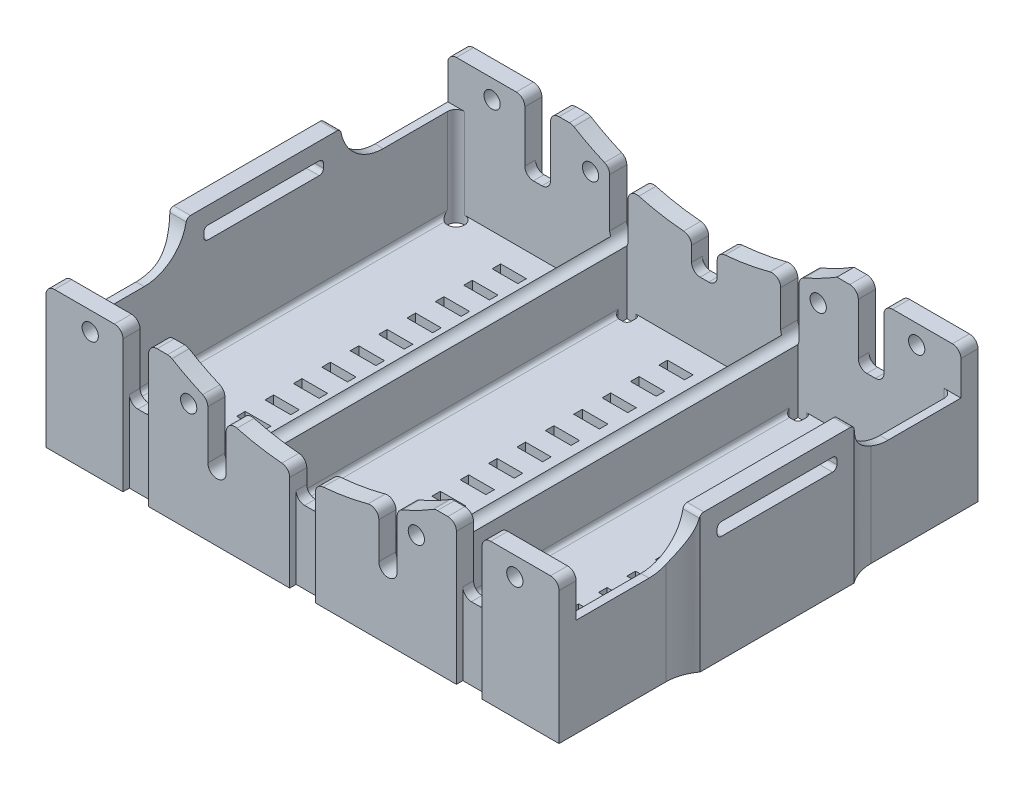
SolidWorks part; units mm, degrees
ref_plane "Front Plane" through (0, 0, 0) normal (0, 0, 1) x (1, 0, 0)
ref_plane "Top Plane" through (0, 0, 0) normal (0, 1, 0) x (1, 0, 0)
ref_plane "Right Plane" through (0, 0, 0) normal (1, 0, 0) x (0, 0, -1)
sketch "Sketch1" plane through (0, 0, 0) normal (0, 1, 0) x (1, 0, 0)
  line L1 (-60, -49) -> (60, -49)
  line L2 (-60, -49) -> (-60, 49)
  line L3 (-60, 49) -> (60, 49)
  line L4 (60, -49) -> (60, 49)
  line L5 (-60, -49) -> (60, 49) construction
  line L6 (-60, 49) -> (60, -49) construction
  point P0 (0, 0)
  dimension "D1" = 120
  dimension "D2" = 98
extrude "Boss-Extrude1" add sketch "Sketch1" along normal blind 2
sketch "Sketch3" plane through (0, 2, 0) normal (0, 1, 0) x (1, 0, 0)
  line L0 (20, 49) -> (20, 68.7594) construction
  line L1 (20, 68.7594) -> (-20, 68.7594) construction
  line L2 (60, 49) -> (-60, 49) construction
  line L3 (-21.8986, 49) -> (-18.1014, 49) construction
  line L4 (-21.8986, 49) -> (-21.8986, -49) construction
  line L5 (-60, -49) -> (60, -49) construction
  line L6 (-20, 68.7594) -> (-20, 49) construction
  line L7 (-18.1014, 49) -> (-18.1014, -49) construction
  line L8 (-18.1014, -49) -> (18.1014, 49) construction
  line L9 (18.1014, 49) -> (18.1014, -49) construction
  line L10 (18.1014, 49) -> (21.8986, 49) construction
  line L11 (21.8986, 49) -> (21.8986, -49) construction
  line L12 (0, 0) -> (0, 49) construction
  line L13 (-18.1014, 49) -> (-16.3514, 49) construction
  line L14 (-18.1014, 49) -> (-18.1014, -49) construction
  line L15 (-18.1014, -49) -> (-16.3514, -49) construction
  line L16 (-16.3514, 49) -> (-16.3514, -49) construction
  line L17 (-23.6486, 49) -> (-21.8986, 49) construction
  line L18 (-23.6486, 49) -> (-23.6486, -49) construction
  line L19 (-23.6486, -49) -> (-21.8986, -49) construction
  line L20 (-21.8986, 49) -> (-21.8986, -49) construction
  line L21 (21.8986, 49) -> (21.8986, -49) construction
  line L22 (23.6486, -49) -> (21.8986, -49) construction
  line L23 (23.6486, 49) -> (23.6486, -49) construction
  line L24 (23.6486, 49) -> (21.8986, 49) construction
  line L25 (16.3514, 49) -> (16.3514, -49) construction
  line L26 (18.1014, -49) -> (16.3514, -49) construction
  line L27 (18.1014, 49) -> (18.1014, -49) construction
  line L28 (18.1014, 49) -> (16.3514, 49) construction
  line L30 (-21.8986, 49) -> (-18.1014, 49)
  line L31 (-21.8986, 49) -> (-21.8986, -49)
  line L32 (-21.8986, -49) -> (-18.1014, -49)
  line L33 (-18.1014, 49) -> (-18.1014, -49)
  line L34 (18.1014, -49) -> (21.8986, -49)
  line L35 (18.1014, -49) -> (18.1014, 49)
  line L36 (18.1014, 49) -> (21.8986, 49)
  line L37 (21.8986, -49) -> (21.8986, 49)
  dimension "D1" = 3.7973
  dimension "D2" = 40
  dimension "D3" = 1.75
extrude "Boss-Extrude3" add sketch "Sketch3" along normal blind 21
sketch "Sketch4" plane through (0, 2, 0) normal (0, 1, 0) x (1, 0, 0)
  line L1 (-60, 49) -> (-21.8986, 49)
  line L2 (-60, 49) -> (-60, 45)
  line L3 (-60, 45) -> (-21.8986, 45)
  line L4 (-21.8986, 49) -> (-21.8986, 45)
  line L6 (-18.1014, 49) -> (18.1014, 49)
  line L7 (-18.1014, 49) -> (-18.1014, 45)
  line L8 (-18.1014, 45) -> (18.1014, 45)
  line L9 (18.1014, 49) -> (18.1014, 45)
  line L10 (60, -49) -> (60, 49) construction
  line L11 (21.8986, 49) -> (60, 49)
  line L12 (21.8986, 49) -> (21.8986, 45)
  line L13 (21.8986, 45) -> (60, 45)
  line L14 (60, 49) -> (60, 45)
  line L15 (-18.1014, -49) -> (-18.1014, 49) construction
  line L16 (-21.8986, 49) -> (-21.8986, -49) construction
  line L17 (21.8986, -49) -> (21.8986, 49) construction
  line L18 (18.1014, 49) -> (18.1014, -49) construction
  line L19 (18.1014, 49) -> (-18.1014, 49) construction
  line L20 (18.1014, 49) -> (18.1014, -49) construction
  line L21 (-60, -49) -> (-21.8986, -49)
  line L22 (-60, -49) -> (-60, -45)
  line L23 (-60, -45) -> (-21.8986, -45)
  line L24 (-21.8986, -49) -> (-21.8986, -45)
  line L25 (-18.1014, -49) -> (18.1014, -49)
  line L26 (-18.1014, -49) -> (-18.1014, -45)
  line L27 (-18.1014, -45) -> (18.1014, -45)
  line L28 (18.1014, -49) -> (18.1014, -45)
  line L30 (21.8986, -49) -> (60, -49)
  line L31 (21.8986, -49) -> (21.8986, -45)
  line L32 (21.8986, -45) -> (60, -45)
  line L33 (60, -49) -> (60, -45)
  dimension "D1" = 4
extrude "Boss-Extrude4" add sketch "Sketch4" along normal up to surface (21 mm away) up to face at (-20, 23, 0)
sketch "Sketch5" plane through (0, 0, 49) normal (0, 0, 1) x (1, 0, 0)
  line L0 (-22.1487, 15.8) -> (-22.1487, 23)
  line L1 (-22.1487, 23) -> (-17.8514, 23)
  line L2 (-17.8514, 23) -> (-17.8514, 15.8)
  line L3 (-60, 23) -> (60, 23) construction
  line L4 (17.8514, 15.8) -> (17.8514, 23)
  line L6 (17.8514, 23) -> (22.1487, 23)
  line L7 (22.1487, 23) -> (22.1487, 15.8)
  line L8 (-60, 23) -> (60, 23) construction
  circle A2 centre (20, 15.8) radius 1.8986 construction
  circle A3 centre (-20, 15.8) radius 1.8986 construction
  arc A6 (-22.1487, 15.8) -> (-17.8514, 15.8) centre (-20, 15.8) ccw
  arc A7 (17.8514, 15.8) -> (22.1487, 15.8) centre (20, 15.8) ccw
  circle A9 centre (-20, 15.8) radius 2.1486 construction
  circle A10 centre (20, 15.8) radius 2.1486 construction
  point P14 (-17.9452, 16.4282)
  point P18 (22.0548, 16.4282)
  dimension "D1" = 0.25
extrude "Cut-Extrude1" cut sketch "Sketch5" against normal through all both and the other way through all
sketch "Sketch6" plane through (0, 2, 0) normal (0, 1, 0) x (1, 0, 0)
  line L0 (-60, 45) -> (-21.8986, 45) construction
  line L1 (-60, -49) -> (-58.1, -49)
  line L2 (-60, -49) -> (-60, 45)
  line L3 (-60, 45) -> (-58.1, 45)
  line L4 (-58.1, -49) -> (-58.1, 45)
  line L5 (21.8986, 45) -> (60, 45) construction
  line L6 (60, -49) -> (58.1, -49)
  line L7 (60, -49) -> (60, 45)
  line L8 (60, 45) -> (58.1, 45)
  line L9 (58.1, -49) -> (58.1, 45)
  dimension "D1" = 1.9
extrude "Boss-Extrude5" add sketch "Sketch6" along normal up to surface (21 mm away) up to face at (-41.0743, 23, -47)
sketch "Sketch9" plane through (0, 0, -45) normal (0, 0, 1) x (1, 0, 0)
  line L1 (0, 24.2) -> (0, 44.7462) construction
  line L2 (-30.9994, 33) -> (-60, 33)
  line L4 (-60, 23) -> (-60, 0) construction
  line L5 (-60, 33) -> (-60, 23)
  line L6 (-60, 23) -> (60, 23)
  line L7 (-17.8514, 23) -> (17.8514, 23) construction
  line L8 (0, 23) -> (0, 24.2) construction
  line L9 (60, 33) -> (60, 23)
  line L10 (30.9994, 33) -> (60, 33)
  line L11 (-60, 23) -> (-60, 0) construction
  arc A4 (30.9994, 33) -> (-30.9994, 33) centre (0, 83.2) cw
  circle A6 centre (-49.6579, 28.5871) radius 1.8987
  circle A8 centre (49.6579, 28.5871) radius 1.8987
  circle A10 centre (26.625, 25.5492) radius 1.8987
  circle A12 centre (-26.625, 25.5492) radius 1.8987
  dimension "D1" = 10
extrude "Boss-Extrude6" add sketch "Sketch9" against normal up to surface (4 mm away) up to face at (0, 16.4086, -49)
sketch "Sketch10" plane through (0, 0, 49) normal (0, 0, 1) x (1, 0, 0)
  line L0 (60, 23) -> (60, 33) construction
  line L1 (60, 33) -> (30.9994, 33) construction
  line L2 (-30.9994, 33) -> (-60, 33) construction
  line L3 (-60, 33) -> (-60, 23) construction
  line L4 (60, 23) -> (60, 33)
  line L5 (60, 33) -> (30.9994, 33)
  line L6 (-30.9994, 33) -> (-60, 33)
  line L7 (-60, 33) -> (-60, 23)
  line L8 (-60, 23) -> (60, 23)
  circle A0 centre (49.6579, 28.5871) radius 1.8987 construction
  circle A1 centre (26.625, 25.5492) radius 1.8987 construction
  circle A2 centre (-26.625, 25.5492) radius 1.8987 construction
  circle A3 centre (-49.6579, 28.5871) radius 1.8987 construction
  arc A4 (-30.9994, 33) -> (30.9994, 33) centre (0, 83.2) ccw construction
  circle A5 centre (49.6579, 28.5871) radius 1.8987
  circle A6 centre (26.625, 25.5492) radius 1.8987
  circle A7 centre (-26.625, 25.5492) radius 1.8987
  circle A8 centre (-49.6579, 28.5871) radius 1.8987
  arc A9 (-30.9994, 33) -> (30.9994, 33) centre (0, 83.2) ccw
extrude "Boss-Extrude7" add sketch "Sketch10" against normal up to surface (4 mm away) up to face at (-34.0594, 13.4298, 45)
sketch "Sketch11" plane through (0, 0, 49) normal (0, 0, 1) x (1, 0, 0)
  line L0 (-17.8514, 23) -> (-17.8514, 15.8) construction
  line L1 (-22.1487, 23) -> (-17.8514, 23)
  line L2 (-22.1487, 23) -> (-22.1487, 43)
  line L3 (-22.1487, 43) -> (-17.8514, 43)
  line L4 (-17.8514, 23) -> (-17.8514, 43)
  line L6 (22.1487, 23) -> (17.8514, 23)
  line L7 (22.1487, 23) -> (22.1487, 43)
  line L8 (22.1487, 43) -> (17.8514, 43)
  line L9 (17.8514, 23) -> (17.8514, 43)
  dimension "D1" = 20
extrude "Cut-Extrude4" cut sketch "Sketch11" against normal through all both
fillet "Fillet2" radius 2 4 edges at (-58.1, 12.5, 45) (-58.1, 12.5, -45) (58.1, 12.5, 45) (58.1, 12.5, -45)
fillet "Fillet3" radius 2 15 edges at (60, 33, 47) (30.9994, 33, 47) (-30.9994, 33, -47) (-30.9994, 33, 47) (22.1487, 28.5151, 47) (17.8514, 26.9654, 47) (-17.8514, 26.9654, 47) (-22.1487, 28.5151, 47) (-60, 33, 47) (-60, 33, -47) (60, 33, -47) (22.1487, 28.5151, -47) (17.8514, 26.9654, -47) (-22.1487, 28.5151, -47) (-17.8514, 26.9654, -47)
sketch "Sketch12" plane through (0, 2, 0) normal (0, 1, 0) x (1, 0, 0)
  line L0 (0, -45) -> (0, 45) construction
  line L1 (18.1014, -45) -> (-18.1014, -45) construction
  line L2 (-18.1014, 45) -> (18.1014, 45) construction
  line L4 (-3, 39.36) -> (3, 39.36)
  line L5 (-3, 39.36) -> (-3, 37.36)
  line L6 (-3, 37.36) -> (3, 37.36)
  line L7 (3, 39.36) -> (3, 37.36)
  line L10 (-38.9993, 45) -> (-38.9993, -45) construction
  line L11 (-56.1, 45) -> (-21.8986, 45) construction
  line L12 (-21.8986, -45) -> (-56.1, -45) construction
  line L13 (3, 38.36) -> (8.9563, 38.36) construction
  line L14 (-38.9993, 0) -> (0, 0) construction
  line L15 (-19.4997, 0) -> (-19.4997, 39.7197) construction
  line L16 (-3, 32.72) -> (-3, 30.72)
  line L17 (-3, 32.72) -> (3, 32.72)
  line L18 (3, 32.72) -> (3, 30.72)
  line L19 (-3, 30.72) -> (3, 30.72)
  line L20 (-3, 26.08) -> (-3, 24.08)
  line L21 (-3, 26.08) -> (3, 26.08)
  line L22 (3, 26.08) -> (3, 24.08)
  line L23 (-3, 24.08) -> (3, 24.08)
  line L24 (-3, 19.44) -> (-3, 17.44)
  line L25 (-3, 19.44) -> (3, 19.44)
  line L26 (3, 19.44) -> (3, 17.44)
  line L27 (-3, 17.44) -> (3, 17.44)
  line L28 (-3, 12.8) -> (-3, 10.8)
  line L29 (-3, 12.8) -> (3, 12.8)
  line L30 (3, 12.8) -> (3, 10.8)
  line L31 (-3, 10.8) -> (3, 10.8)
  line L32 (-3, 6.16) -> (-3, 4.16)
  line L33 (-3, 6.16) -> (3, 6.16)
  line L34 (3, 6.16) -> (3, 4.16)
  line L35 (-3, 4.16) -> (3, 4.16)
  line L36 (-3, -0.48) -> (-3, -2.48)
  line L37 (-3, -0.48) -> (3, -0.48)
  line L38 (3, -0.48) -> (3, -2.48)
  line L39 (-3, -2.48) -> (3, -2.48)
  line L40 (-3, -7.12) -> (-3, -9.12)
  line L41 (-3, -7.12) -> (3, -7.12)
  line L42 (3, -7.12) -> (3, -9.12)
  line L43 (-3, -9.12) -> (3, -9.12)
  line L44 (-3, -13.76) -> (-3, -15.76)
  line L45 (-3, -13.76) -> (3, -13.76)
  line L46 (3, -13.76) -> (3, -15.76)
  line L47 (-3, -15.76) -> (3, -15.76)
  line L48 (-3, -20.4) -> (-3, -22.4)
  line L49 (-3, -20.4) -> (3, -20.4)
  line L50 (3, -20.4) -> (3, -22.4)
  line L51 (-3, -22.4) -> (3, -22.4)
  line L52 (-3, -27.04) -> (-3, -29.04)
  line L53 (-3, -27.04) -> (3, -27.04)
  line L54 (3, -27.04) -> (3, -29.04)
  line L55 (-3, -29.04) -> (3, -29.04)
  line L56 (-3, -33.68) -> (-3, -35.68)
  line L57 (-3, -33.68) -> (3, -33.68)
  line L58 (3, -33.68) -> (3, -35.68)
  line L59 (-3, -35.68) -> (3, -35.68)
  line L60 (-3, -40.32) -> (-3, -42.32)
  line L61 (-3, -40.32) -> (3, -40.32)
  line L62 (3, -40.32) -> (3, -42.32)
  line L63 (-3, -42.32) -> (3, -42.32)
  line L71 (-35.9993, -42.32) -> (-41.9993, -42.32)
  line L72 (-35.9993, -40.32) -> (-41.9993, -40.32)
  line L73 (-35.9993, -40.32) -> (-35.9993, -42.32)
  line L74 (-35.9993, -35.68) -> (-41.9993, -35.68)
  line L75 (-35.9993, -33.68) -> (-41.9993, -33.68)
  line L76 (-35.9993, -33.68) -> (-35.9993, -35.68)
  line L77 (-41.9993, 39.36) -> (-41.9993, 37.36)
  line L78 (-35.9993, 37.36) -> (-41.9993, 37.36)
  line L79 (-35.9993, 39.36) -> (-41.9993, 39.36)
  line L81 (-41.9993, -40.32) -> (-41.9993, -42.32)
  line L82 (-41.9993, -33.68) -> (-41.9993, -35.68)
  line L83 (-35.9993, -29.04) -> (-41.9993, -29.04)
  line L84 (-41.9993, -27.04) -> (-41.9993, -29.04)
  line L85 (-35.9993, -27.04) -> (-41.9993, -27.04)
  line L86 (-35.9993, -27.04) -> (-35.9993, -29.04)
  line L87 (-35.9993, -22.4) -> (-41.9993, -22.4)
  line L88 (-41.9993, -20.4) -> (-41.9993, -22.4)
  line L89 (-35.9993, -20.4) -> (-41.9993, -20.4)
  line L90 (-35.9993, -20.4) -> (-35.9993, -22.4)
  line L91 (-35.9993, -15.76) -> (-41.9993, -15.76)
  line L92 (-41.9993, -13.76) -> (-41.9993, -15.76)
  line L93 (-35.9993, -13.76) -> (-41.9993, -13.76)
  line L94 (-35.9993, -13.76) -> (-35.9993, -15.76)
  line L95 (-35.9993, -9.12) -> (-41.9993, -9.12)
  line L96 (-41.9993, -7.12) -> (-41.9993, -9.12)
  line L97 (-35.9993, -7.12) -> (-41.9993, -7.12)
  line L98 (-35.9993, -7.12) -> (-35.9993, -9.12)
  line L99 (-35.9993, -2.48) -> (-41.9993, -2.48)
  line L100 (-41.9993, -0.48) -> (-41.9993, -2.48)
  line L101 (-35.9993, -0.48) -> (-41.9993, -0.48)
  line L102 (-35.9993, -0.48) -> (-35.9993, -2.48)
  line L103 (-35.9993, 4.16) -> (-41.9993, 4.16)
  line L104 (-41.9993, 6.16) -> (-41.9993, 4.16)
  line L105 (-35.9993, 6.16) -> (-41.9993, 6.16)
  line L106 (-35.9993, 6.16) -> (-35.9993, 4.16)
  line L107 (-35.9993, 10.8) -> (-41.9993, 10.8)
  line L108 (-41.9993, 12.8) -> (-41.9993, 10.8)
  line L109 (-35.9993, 12.8) -> (-41.9993, 12.8)
  line L110 (-35.9993, 12.8) -> (-35.9993, 10.8)
  line L111 (-35.9993, 17.44) -> (-41.9993, 17.44)
  line L112 (-41.9993, 19.44) -> (-41.9993, 17.44)
  line L113 (-35.9993, 19.44) -> (-41.9993, 19.44)
  line L114 (-35.9993, 19.44) -> (-35.9993, 17.44)
  line L115 (-35.9993, 24.08) -> (-41.9993, 24.08)
  line L116 (-41.9993, 26.08) -> (-41.9993, 24.08)
  line L117 (-35.9993, 26.08) -> (-41.9993, 26.08)
  line L118 (-35.9993, 26.08) -> (-35.9993, 24.08)
  line L119 (-35.9993, 30.72) -> (-41.9993, 30.72)
  line L120 (-41.9993, 32.72) -> (-41.9993, 30.72)
  line L121 (-35.9993, 32.72) -> (-41.9993, 32.72)
  line L122 (-35.9993, 32.72) -> (-35.9993, 30.72)
  line L123 (-35.9993, 39.36) -> (-35.9993, 37.36)
  line L124 (35.9993, 39.36) -> (35.9993, 37.36)
  line L125 (35.9993, 32.72) -> (35.9993, 30.72)
  line L126 (35.9993, 32.72) -> (41.9993, 32.72)
  line L127 (41.9993, 32.72) -> (41.9993, 30.72)
  line L128 (35.9993, 30.72) -> (41.9993, 30.72)
  line L129 (35.9993, 26.08) -> (35.9993, 24.08)
  line L130 (35.9993, 26.08) -> (41.9993, 26.08)
  line L131 (41.9993, 26.08) -> (41.9993, 24.08)
  line L132 (35.9993, 24.08) -> (41.9993, 24.08)
  line L133 (35.9993, 19.44) -> (35.9993, 17.44)
  line L134 (35.9993, 19.44) -> (41.9993, 19.44)
  line L135 (41.9993, 19.44) -> (41.9993, 17.44)
  line L136 (35.9993, 17.44) -> (41.9993, 17.44)
  line L137 (35.9993, 12.8) -> (35.9993, 10.8)
  line L138 (35.9993, 12.8) -> (41.9993, 12.8)
  line L139 (41.9993, 12.8) -> (41.9993, 10.8)
  line L140 (35.9993, 10.8) -> (41.9993, 10.8)
  line L141 (35.9993, 6.16) -> (35.9993, 4.16)
  line L142 (35.9993, 6.16) -> (41.9993, 6.16)
  line L143 (41.9993, 6.16) -> (41.9993, 4.16)
  line L144 (35.9993, 4.16) -> (41.9993, 4.16)
  line L145 (35.9993, -0.48) -> (35.9993, -2.48)
  line L146 (35.9993, -0.48) -> (41.9993, -0.48)
  line L147 (41.9993, -0.48) -> (41.9993, -2.48)
  line L148 (35.9993, -2.48) -> (41.9993, -2.48)
  line L149 (35.9993, -7.12) -> (35.9993, -9.12)
  line L150 (35.9993, -7.12) -> (41.9993, -7.12)
  line L151 (41.9993, -7.12) -> (41.9993, -9.12)
  line L152 (35.9993, -9.12) -> (41.9993, -9.12)
  line L153 (35.9993, -13.76) -> (35.9993, -15.76)
  line L154 (35.9993, -13.76) -> (41.9993, -13.76)
  line L155 (41.9993, -13.76) -> (41.9993, -15.76)
  line L156 (35.9993, -15.76) -> (41.9993, -15.76)
  line L157 (35.9993, -20.4) -> (35.9993, -22.4)
  line L158 (35.9993, -20.4) -> (41.9993, -20.4)
  line L159 (41.9993, -20.4) -> (41.9993, -22.4)
  line L160 (35.9993, -22.4) -> (41.9993, -22.4)
  line L161 (35.9993, -27.04) -> (35.9993, -29.04)
  line L162 (35.9993, -27.04) -> (41.9993, -27.04)
  line L163 (41.9993, -27.04) -> (41.9993, -29.04)
  line L164 (35.9993, -29.04) -> (41.9993, -29.04)
  line L165 (41.9993, -33.68) -> (41.9993, -35.68)
  line L166 (41.9993, -40.32) -> (41.9993, -42.32)
  line L168 (35.9993, 39.36) -> (41.9993, 39.36)
  line L169 (35.9993, 37.36) -> (41.9993, 37.36)
  line L170 (41.9993, 39.36) -> (41.9993, 37.36)
  line L171 (35.9993, -33.68) -> (35.9993, -35.68)
  line L172 (35.9993, -33.68) -> (41.9993, -33.68)
  line L173 (35.9993, -35.68) -> (41.9993, -35.68)
  line L174 (35.9993, -40.32) -> (35.9993, -42.32)
  line L175 (35.9993, -40.32) -> (41.9993, -40.32)
  line L176 (35.9993, -42.32) -> (41.9993, -42.32)
  point P22 (0, 39.36)
  dimension "D1" = 6
  dimension "D2" = 6.64
  dimension "D3" = 2
  dimension "D4" = 13
extrude "Cut-Extrude5" cut sketch "Sketch12" against normal through all both
sketch "Sketch13" plane through (0, 0, 49) normal (0, 0, 1) x (1, 0, 0)
  line L0 (41.9993, 2) -> (35.9993, 2) construction
  line L1 (3, 2) -> (-3, 2) construction
  line L2 (-35.9993, 2) -> (-41.9993, 2) construction
  line L3 (41.9993, 2) -> (35.9993, 2) construction
  line L4 (3, 2) -> (-3, 2) construction
  line L5 (-35.9993, 2) -> (-41.9993, 2) construction
  line L6 (-41.9993, 17) -> (-35.9993, 17)
  line L7 (-3, 17) -> (-35.9993, 17) construction
  line L8 (-3, 17) -> (3, 17)
  line L9 (-35.9993, 17) -> (-3, 2) construction
  line L10 (35.9993, 17) -> (41.9993, 17)
  line L11 (-3, 17) -> (-3, 2) construction
  line L12 (3, 17) -> (35.9993, 17) construction
  line L13 (-35.9993, 17) -> (-35.9993, 2) construction
  line L14 (-35.9993, 2) -> (-41.9993, 17) construction
  line L15 (-41.9993, 17) -> (-41.9993, 2) construction
  line L16 (-3, 2) -> (3, 17) construction
  line L17 (3, 17) -> (3, 2) construction
  line L18 (-41.9993, 17) -> (-41.9993, 47)
  line L19 (-41.9993, 47) -> (-35.9993, 47)
  line L20 (-35.9993, 47) -> (-35.9993, 17)
  line L21 (-3, 17) -> (-3, 47)
  line L22 (-3, 47) -> (3, 47)
  line L23 (3, 47) -> (3, 17)
  line L24 (35.9993, 17) -> (35.9993, 47)
  line L25 (35.9993, 47) -> (41.9993, 47)
  line L26 (41.9993, 47) -> (41.9993, 17)
  dimension "D1" = 15
  dimension "D2" = 30
extrude "Cut-Extrude6" cut sketch "Sketch13" against normal through all both
sketch "Sketch19" plane through (0, 17, 0) normal (0, 1, 0) x (1, 0, 0)
  line L5 (-35.9993, 49) -> (-35.9993, 45) construction
  line L6 (-41.9993, 49) -> (-35.9993, 49)
  line L7 (-41.9993, 49) -> (-41.9993, 47.5)
  line L8 (-41.9993, 47.5) -> (-35.9993, 47.5)
  line L9 (-35.9993, 49) -> (-35.9993, 47.5)
  line L10 (3, 45) -> (3, 49) construction
  line L11 (-3, 49) -> (3, 49)
  line L12 (-3, 49) -> (-3, 47.5)
  line L13 (-3, 47.5) -> (3, 47.5)
  line L14 (3, 49) -> (3, 47.5)
  line L15 (41.9993, 45) -> (41.9993, 49) construction
  line L16 (35.9993, 49) -> (41.9993, 49)
  line L17 (35.9993, 49) -> (35.9993, 47.5)
  line L18 (35.9993, 47.5) -> (41.9993, 47.5)
  line L19 (41.9993, 49) -> (41.9993, 47.5)
  line L20 (0, 0) -> (11.3492, 0) construction
  line L21 (41.9993, -49) -> (41.9993, -47.5)
  line L22 (35.9993, -47.5) -> (41.9993, -47.5)
  line L23 (35.9993, -49) -> (35.9993, -47.5)
  line L24 (35.9993, -49) -> (41.9993, -49)
  line L25 (3, -49) -> (3, -47.5)
  line L26 (-3, -47.5) -> (3, -47.5)
  line L27 (-3, -49) -> (-3, -47.5)
  line L28 (-3, -49) -> (3, -49)
  line L29 (-35.9993, -49) -> (-35.9993, -47.5)
  line L30 (-41.9993, -47.5) -> (-35.9993, -47.5)
  line L31 (-41.9993, -49) -> (-41.9993, -47.5)
  line L32 (-41.9993, -49) -> (-35.9993, -49)
  dimension "D1" = 1.5
extrude "Cut-Extrude9" cut sketch "Sketch19" against normal through all
fillet "Fillet4" radius 2 24 edges at (41.9993, 33, -47) (41.9993, 17, -46.25) (35.9993, 33, -47) (35.9993, 17, -46.25) (3, 24.2763, -47) (-3, 24.2763, -47) (-3, 17, -46.25) (3, 17, -46.25) (-35.9993, 33, -47) (-35.9993, 17, -46.25) (-41.9993, 33, -47) (-41.9993, 17, -46.25) (41.9993, 33, 47) (41.9993, 17, 46.25) (35.9993, 33, 47) (35.9993, 17, 46.25) (-3, 17, 46.25) (3, 17, 46.25) (3, 24.2763, 47) (-3, 24.2763, 47) (-35.9993, 33, 47) (-35.9993, 17, 46.25) (-41.9993, 17, 46.25) (-41.9993, 33, 47)
sketch "Sketch14" plane through (0, 2, 0) normal (0, 1, 0) x (1, 0, 0)
  line L0 (0, 45) -> (0, -45) construction
  line L1 (-18.1014, 45) -> (18.1014, 45) construction
  line L2 (18.1014, -45) -> (-18.1014, -45) construction
  line L3 (0, -45) -> (-58.1, 0) construction
  line L4 (-58.1, -43) -> (-58.1, 43) construction
  line L5 (-58.1, 0) -> (0, 0) construction
  line L6 (-18.1014, 45) -> (18.1014, 45) construction
  line L7 (24.8986, 45) -> (24.8986, 42)
  line L8 (-18.1014, 45) -> (-15.1014, 45)
  line L9 (-18.1014, 45) -> (-18.1014, 42)
  line L10 (-18.1014, 42) -> (-15.1014, 42)
  line L11 (-15.1014, 45) -> (-15.1014, 42)
  line L12 (-21.8986, 45) -> (-24.8986, 45)
  line L13 (-21.8986, 45) -> (-21.8986, 42)
  line L14 (-21.8986, 42) -> (-24.8986, 42)
  line L15 (-24.8986, 45) -> (-24.8986, 42)
  line L16 (21.8986, 42) -> (24.8986, 42)
  line L17 (21.8986, 45) -> (21.8986, 42)
  line L18 (21.8986, 45) -> (24.8986, 45)
  line L19 (15.1014, 45) -> (15.1014, 42)
  line L20 (18.1014, 42) -> (15.1014, 42)
  line L21 (18.1014, 45) -> (18.1014, 42)
  line L22 (18.1014, 45) -> (15.1014, 45)
  line L23 (-18.1014, -45) -> (18.1014, -45) construction
  line L24 (18.1014, -45) -> (15.1014, -45)
  line L25 (18.1014, -45) -> (18.1014, -42)
  line L26 (18.1014, -42) -> (15.1014, -42)
  line L27 (15.1014, -45) -> (15.1014, -42)
  line L28 (21.8986, -45) -> (24.8986, -45)
  line L29 (21.8986, -45) -> (21.8986, -42)
  line L30 (21.8986, -42) -> (24.8986, -42)
  line L31 (-24.8986, -45) -> (-24.8986, -42)
  line L32 (-21.8986, -42) -> (-24.8986, -42)
  line L33 (-21.8986, -45) -> (-21.8986, -42)
  line L34 (-21.8986, -45) -> (-24.8986, -45)
  line L35 (-15.1013, -45) -> (-15.1013, -42)
  line L36 (-18.1013, -42) -> (-15.1013, -42)
  line L37 (-18.1014, -45) -> (-18.1013, -42)
  line L38 (-18.1014, -45) -> (-15.1013, -45)
  line L39 (24.8986, -45) -> (24.8986, -42)
  circle A0 centre (-56.1, 43) radius 2
  arc A5 (-56.1, 45) -> (-58.1, 43) centre (-56.1, 43) ccw construction
  circle A6 centre (56.1, 43) radius 2
  circle A7 centre (56.1, -43) radius 2
  circle A8 centre (-56.1, -43) radius 2
  dimension "D1" = 3
extrude "Cut-Extrude7" cut sketch "Sketch14" against normal through all both
fillet "Fillet5" radius 1 24 edges at (-15.1013, 1, 45) (-15.1013, 1, 42) (-24.8986, 1, 45) (-24.8986, 1, 42) (15.1014, 1, 42) (15.1014, 1, 45) (24.8986, 1, 42) (24.8986, 1, 45) (24.8986, 1, -42) (24.8986, 1, -45) (15.1014, 1, -45) (15.1014, 1, -42) (-15.1014, 1, -45) (-15.1014, 1, -42) (-24.8986, 1, -42) (-24.8986, 1, -45) (-21.8986, 1, 42) (-18.1013, 1, 42) (18.1014, 1, 42) (21.8986, 1, 42) (18.1014, 1, -42) (21.8986, 1, -42) (-18.1014, 1, -42) (-21.8986, 1, -42)
sketch "Sketch16" plane through (0, 0, 0) normal (0, -1, 0) x (1, 0, 0)
  line L0 (-60, 0) -> (-76.8023, 0) construction
  line L1 (-60, -49) -> (-60, 49) construction
  line L2 (-76.8023, 14) -> (-76.8023, -14) construction
  line L3 (-62, -18) -> (-60, -18)
  line L4 (-62, -18) -> (-62, 18)
  line L5 (-62, 18) -> (-60, 18)
  line L6 (-60, -18) -> (-60, 18)
  line L7 (0, 0) -> (0, 45.5427) construction
  line L9 (62, 18) -> (60, 18)
  line L10 (60, -18) -> (60, 18)
  line L11 (62, -18) -> (60, -18)
  line L12 (62, -18) -> (62, 18)
  point P9 (-60, 0)
  point P11 (-76.8023, 0)
  point P15 (0, 45.5427)
  dimension "D1" = 2
  dimension "D2" = 4
  dimension "D3" = 28
extrude "Boss-Extrude8" add sketch "Sketch16" against normal up to surface (23 mm away)
sketch "Sketch17" plane through (0, 23, 0) normal (0, 1, 0) x (1, 0, 0)
  line L0 (-62, 18) -> (-58.1, 18)
  line L1 (-58.1, -43) -> (-58.1, 43) construction
  line L2 (-58.1, 18) -> (-58.1, -18)
  line L3 (-58.1, -43) -> (-58.1, 43) construction
  line L4 (-58.1, -18) -> (-62, -18)
  line L5 (-62, -18) -> (-62, 18)
  line L6 (-60, -18) -> (-62, -18) construction
  line L7 (0, 0) -> (0, 28.2857) construction
  line L8 (58.1, -18) -> (62, -18)
  line L9 (58.1, 18) -> (58.1, -18)
  line L10 (62, 18) -> (58.1, 18)
  line L11 (62, -18) -> (62, 18)
extrude "Boss-Extrude9" add sketch "Sketch17" along normal blind 9
sketch "Sketch18" plane through (-62, 0, 0) normal (-1, 0, 0) x (0, 0, 1)
  line L0 (-45, 23) -> (-18, 23) construction
  line L1 (-14, 28) -> (14, 28)
  line L2 (-14, 28) -> (-14, 25)
  line L3 (-14, 25) -> (14, 25)
  line L4 (14, 28) -> (14, 25)
  line L5 (-45, 23) -> (-18, 23) construction
  line L6 (0, 0) -> (0, 25) construction
  line L7 (-18, 32) -> (-18, 0) construction
  line L8 (-18, 32) -> (18, 32) construction
  dimension "D1" = 4
  dimension "D2" = 4
  dimension "D3" = 3
extrude "Cut-Extrude8" cut sketch "Sketch18" against normal through all
fillet "Fillet6" radius 10 16 edges at (-61, 0, -18) (-61, 0, 18) (-60, 11.5, -18) (-60, 11.5, 18) (61, 0, 18) (61, 0, -18) (60, 11.5, 18) (60, 11.5, -18) (-59.05, 23, 18) (-58.1, 27.5, 18) (-59.05, 23, -18) (-58.1, 27.5, -18) (58.1, 27.5, -18) (59.05, 23, 18) (58.1, 27.5, 18) (59.05, 23, -18)
fillet "Fillet7" radius 1 12 edges at (60.05, 32, -18) (60.05, 32, 18) (60.05, 25, 14) (60.05, 25, -14) (-60.05, 32, 18) (-60.05, 32, -18) (-60.05, 28, 14) (-60.05, 25, 14) (-60.05, 28, -14) (-60.05, 25, -14) (60.05, 28, -14) (60.05, 28, 14)
fillet "Fillet8" radius 1 6 edges at (58.1, 2, 0) (21.8986, 2, 0) (18.1014, 2, 0) (-18.1014, 2, 0) (-21.8986, 2, 0) (-58.1, 2, 0)
